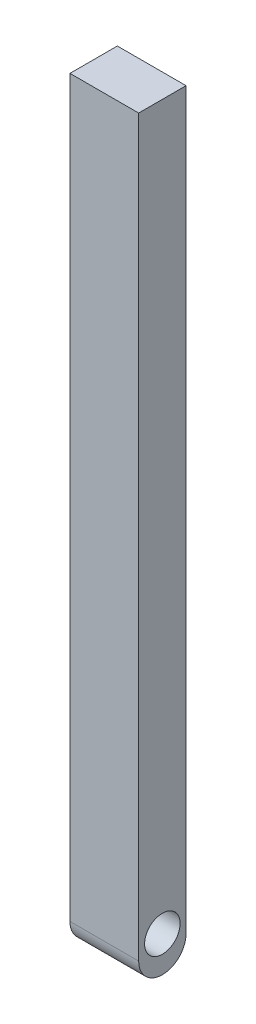
SolidWorks part; units mm, degrees
ref_plane "Plan de face" through (0, 0, 0) normal (0, 0, 1) x (1, 0, 0)
ref_plane "Plan de dessus" through (0, 0, 0) normal (0, 1, 0) x (1, 0, 0)
ref_plane "Plan de droite" through (0, 0, 0) normal (1, 0, 0) x (0, 0, -1)
sketch "Esquisse1" plane through (0, 0, 0) normal (0, 0, 1) x (1, 0, 0)
  line L0 (-2.1382, 10.1768) -> (0.7618, 10.1768)
  line L1 (-2.1382, 10.1768) -> (-2.1382, -21.8232)
  line L2 (0.7618, 10.1768) -> (0.7618, -21.8232)
  line L3 (-2.1382, -21.8232) -> (0.7618, -21.8232)
  dimension "D1" = 2.9
  dimension "D2" = 32
extrude "Boss.-Extru.1" add sketch "Esquisse1" along normal blind 2
fillet "Congé1" radius 1 2 edges at (-0.6882, -21.8232, 2) (-0.6882, -21.8232, 0)
sketch "Esquisse2" plane through (0.7618, 0, 0) normal (1, 0, 0) x (0, 0, -1)
  circle A0 centre (-1, -20.3232) radius 0.75
  dimension "D1" = 1.5
  dimension "D2" = 1
extrude "Enlèv. mat.-Extru.1" cut sketch "Esquisse2" against normal blind 3
